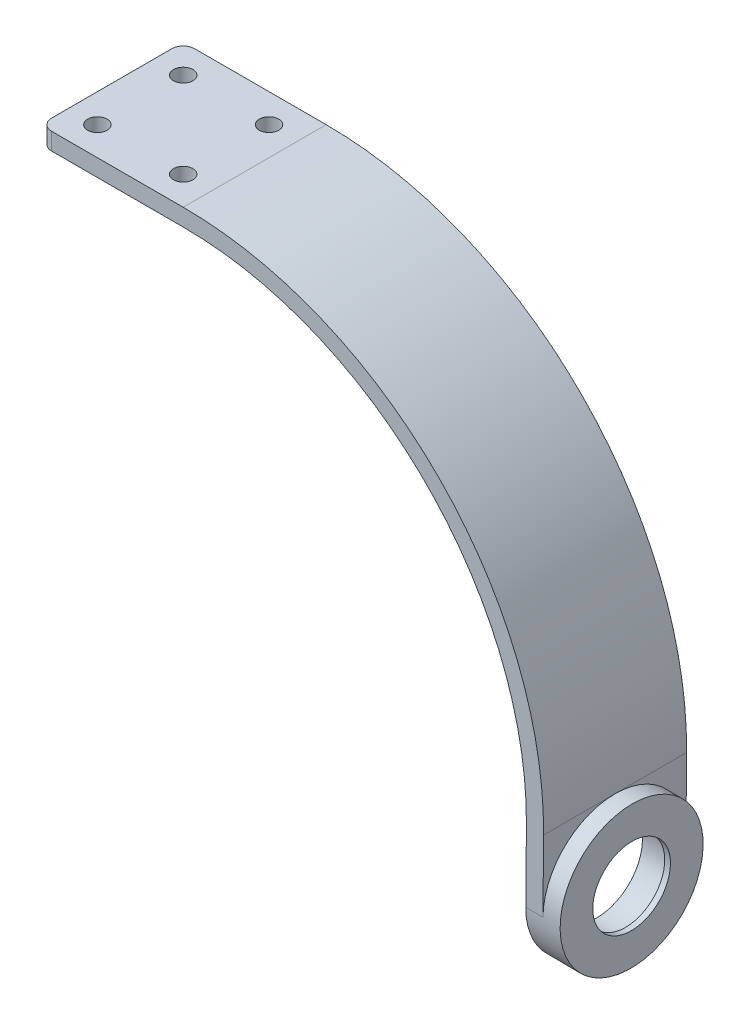
SolidWorks part; units mm, degrees
ref_plane "Front Plane" through (0, 0, 0) normal (0, 0, 1) x (1, 0, 0)
ref_plane "Top Plane" through (0, 0, 0) normal (0, 1, 0) x (1, 0, 0)
ref_plane "Right Plane" through (0, 0, 0) normal (1, 0, 0) x (0, 0, -1)
sketch "Sketch2" plane through (0, 0, 0) normal (0, 0, 1) x (1, 0, 0)
  line L0 (0, 0) -> (0, 60) construction
  line L1 (0, 0) -> (59.9977, -0.5236) construction
  line L4 (0, 63) -> (-25, 63)
  line L5 (-25, 63) -> (-25, 60)
  line L6 (-25, 60) -> (0, 60)
  line L7 (59.9977, -0.5236) -> (59.7796, -25.5226)
  line L8 (59.7796, -25.5226) -> (62.7794, -25.5488)
  line L9 (62.7794, -25.5488) -> (62.9976, -0.5498)
  arc A0 (0, 60) -> (59.9977, -0.5236) centre (0, 0) cw
  arc A1 (0, 63) -> (62.9976, -0.5498) centre (0, 0) cw
  dimension "D2" = 60
  dimension "D1" = 90.5
  dimension "D3" = 3
  dimension "D4" = 25
  dimension "D5" = 25
extrude "Boss-Extrude1" add sketch "Sketch2" along normal blind 25
sketch "Sketch3" plane through (0, 63, 0) normal (0, 1, 0) x (1, 0, 0)
  line L0 (-25, -25) -> (-25, 0) construction
  line L1 (-20, -5) -> (-5, -5) construction
  line L2 (-20, -5) -> (-20, -20) construction
  line L3 (-20, -20) -> (-5, -20) construction
  line L4 (-5, -5) -> (-5, -20) construction
  line L5 (-20, -5) -> (-5, -20) construction
  line L6 (-20, -20) -> (-5, -5) construction
  line L7 (0, -25) -> (-25, -25) construction
  line L8 (0, 0) -> (-25, 0) construction
  point P0 (-20, -5)
  point P1 (-5, -20)
  point P2 (-20, -20)
  point P3 (-5, -5)
  point P4 (-12.5, -12.5)
  dimension "D1" = 5
  dimension "D2" = 5
  dimension "D3" = 5
hole_wizard "M3 Clearance Hole1" positions "Sketch3" profile "Sketch5" hole size "M3" standard "ANSI Metric"
sketch "Sketch5" plane through (-20, 63, 5) normal (1, 0, 0) x (0, 0, 1)
  line L0 (0, 0) -> (0, 3)
  line L1 (0, 3) -> (1.7, 3)
  line L2 (1.7, 3) -> (1.7, 0)
  line L5 (1.7, 0) -> (0, 0)
  line L11 (0, -6.35) -> (0, 107.95) construction
  dimension "Thru Hole Dia." = 3.4
  dimension "Thru Hole Depth" = 3
sketch "Sketch6" plane through (62.9976, -0.5498, 0) normal (1, -0.0087, 0) x (0, 0, -1)
  line L1 (-25, 0) -> (0, -25) construction
  line L4 (0, 0) -> (-25, -25) construction
  circle A1 centre (-12.5, -12.5) radius 7.89
  dimension "D1" = 15.78
extrude "Cut-Extrude1" cut sketch "Sketch6" along direction (-1, 0.0087, 0) on the side against the normal up to next (3 mm away)
fillet "Fillet1" radius 12.5 2 edges at (61.2795, -25.5357, 0) (61.2795, -25.5357, 25)
fillet "Fillet2" radius 2 2 edges at (-25, 61.5, 25) (-25, 61.5, 0)
sketch "Sketch7" plane through (62.9976, -0.5498, 0) normal (1, -0.0087, 0) x (0, 0, -1)
  circle A0 centre (-12.5, -12.5) radius 6.79
  circle A1 centre (-12.5, -12.5) radius 12.5
  dimension "D1" = 13.58
  dimension "D2" = 25
extrude "Boss-Extrude2" add sketch "Sketch7" along normal blind 3
sketch "Sketch9" plane through (59.9977, -0.5236, 0) normal (-1, 0.0087, 0) x (0, 0, 1)
  circle A0 centre (12.5, -12.5) radius 7.89
  dimension "D1" = 15.78
extrude "Cut-Extrude2" cut sketch "Sketch9" against normal blind 5
equation "\"D1@Sketch2\"=362/4"
equation "\"D2@Sketch3\"=\"D1@Sketch3\""
equation "\"D3@Sketch3\"=\"D1@Sketch3\""
